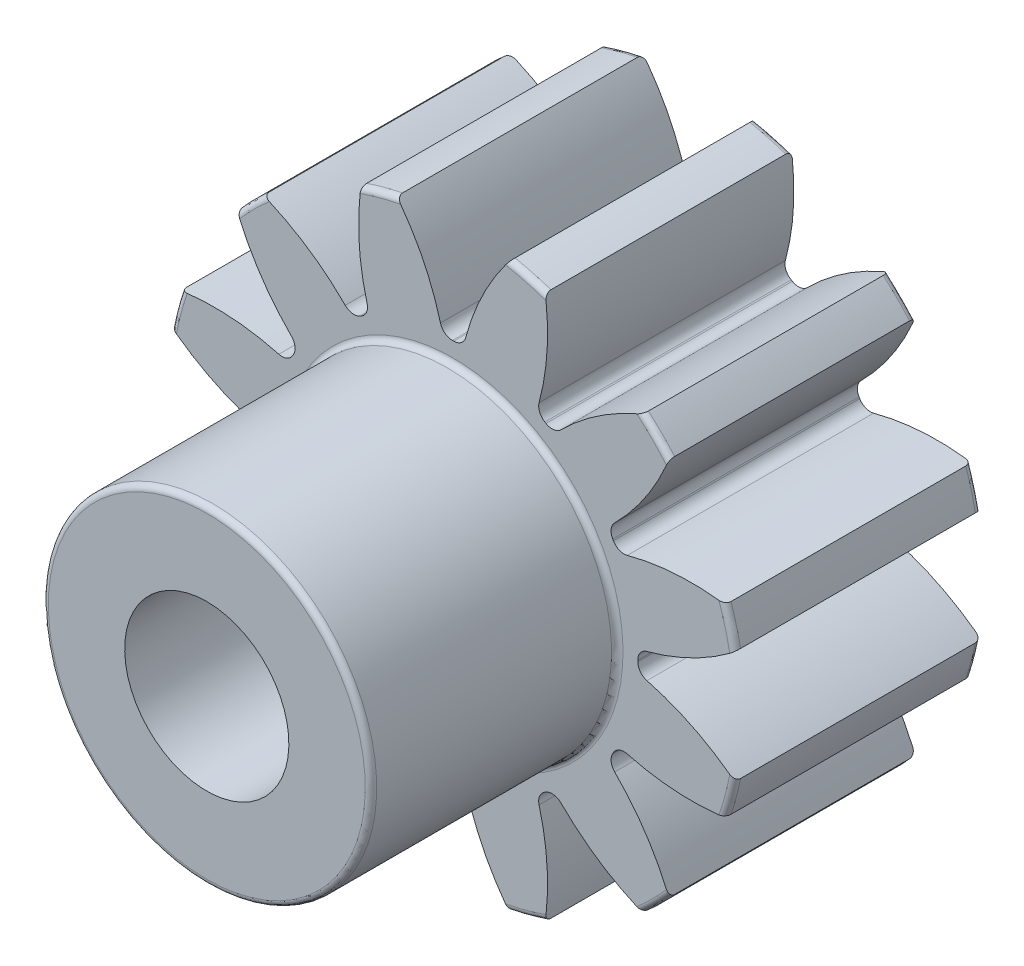
SolidWorks part; units mm, degrees
material "Delrin 2700 NC010, Low Viscosity Acetal Copolymer (SS)"
ref_plane "Front Plane" through (0, 0, 0) normal (0, 0, 1) x (1, 0, 0)
ref_plane "Top Plane" through (0, 0, 0) normal (0, 1, 0) x (1, 0, 0)
ref_plane "Right Plane" through (0, 0, 0) normal (1, 0, 0) x (0, 0, -1)
sketch "Sketch1" plane through (0, 0, 0) normal (0, 0, 1) x (1, 0, 0)
  line L0 (-152.4, 0) -> (152.4, 0) construction
  circle A0 centre (0, 0) radius 7 construction
  circle A1 centre (0, 0) radius 6 construction
  circle A2 centre (0, 0) radius 4.5 construction
  circle A3 centre (0, 0) radius 4 construction
  circle A4 centre (0, 0) radius 2 construction
  dimension "D2" = 1
  dimension "D3" = 2.5
  dimension "D1" = 2.5
sketch "Sketch2" plane through (0, 0, 0) normal (1, 0, 0) x (0, 0, -1)
  line L0 (0, 0) -> (-6, 0) construction
  line L1 (-6, 0) -> (-12, 0) construction
  dimension "Overall Width" = 12
  dimension "Face Width" = 6
sketch "Sketch4" plane through (0, 0, 0) normal (1, 0, 0) x (0, 0, -1)
  line L0 (-12, 2) -> (-12, 4)
  line L1 (-12, 4) -> (-6, 4)
  line L2 (-6, 4) -> (-6, 7)
  line L3 (-6, 7) -> (0, 7)
  line L4 (0, 7) -> (0, 2)
  line L5 (-6, 4) -> (-6, 0) construction
  line L6 (0, 7) -> (0, -7) construction
  line L7 (-6, 4) -> (0, 4) construction
  line L12 (-12, 2) -> (0, 2)
revolve "Revolve1" add sketch "Sketch4" angle 360 about L1
fillet "Fillet2" radius 0.14 4 edges at (0, 4, 12) (0, 4, 6) (0, 7, 6) (0, 7, 0)
sketch "Sketch7" plane through (0, 0, 6) normal (0, 0, 1) x (1, 0, 0)
  line L0 (0, 0) -> (0, 7) construction
  line L1 (0.7832, 5.9487) -> (1.27, 6.8838) construction
  line L3 (1.8117, 6.7615) -> (1.5529, 5.7956) construction
  line L4 (1.5529, 5.7956) -> (1.1647, 4.3467) construction
  line L5 (0, 0) -> (1.1647, 4.3467) construction
  line L6 (0.7832, 5.9487) -> (0, 0) construction
  line L7 (0.7832, 5.9487) -> (0.9137, 6.9401) construction
  line L8 (0.7832, 5.9487) -> (0, 0) construction
  circle A0 centre (0, 0) radius 7 construction
  arc A1 (-0.0164, 4.5) -> (0.0164, 4.5) centre (0, 0) cw
  circle A2 centre (0, 0) radius 4.5 construction
  arc A3 (-0.7832, 5.9487) -> (0.7832, 5.9487) centre (0, 0) cw construction
  circle A4 centre (0, 0) radius 6 construction
  arc A5 (2.2448, 6.6303) -> (1.3711, 6.8644) centre (0, 0) ccw construction
  arc A6 (0.7832, 5.9487) -> (2.2961, 5.5433) centre (0, 0) cw construction
  arc A7 (-1.3711, 6.8644) -> (1.3711, 6.8644) centre (0, 0) cw
  arc A8 (0.3074, 4.7228) -> (1.3711, 6.8644) centre (6.1052, 3.1782) cw
  arc A9 (-0.3074, 4.7228) -> (-1.3711, 6.8644) centre (-6.1052, 3.1782) ccw
  arc A10 (-0.0164, 4.5) -> (-0.3074, 4.7228) centre (-0.0175, 4.8) cw
  arc A11 (0.0164, 4.5) -> (0.3074, 4.7228) centre (0.0175, 4.8) ccw
  point P26 (-0.2511, 4.493)
  point P29 (0.2511, 4.493)
  dimension "D4" = 0.3
  dimension "D5" = 6
  dimension "D3" = 20
  dimension "D1" = 3.1416
  dimension "D2" = 1.5708
extrude "Cut-Extrude2" cut sketch "Sketch7" against normal through all
pattern_circular "CirPattern1" count 12 over 360 about axis through (0, 0, 12) along (0, 0, -1) of "Cut-Extrude2"
equation "\"D1@Sketch1\"=2.5*(\"Pitch Dia.@Sketch1\"/\"Number of Teeth@Sketch1\")"
equation "\"D1@CirPattern1\"=\"Number of Teeth@Sketch1\""
equation "\"D1@Fillet2\"=\"OD@Sketch1\"*.01"
equation "\"D1@Sketch7\"=3.14159*(\"Pitch Dia.@Sketch1\"/\"Number of Teeth@Sketch1\")"
equation "\"D2@Sketch7\"=\"D1@Sketch7\"/2"
equation "\"D4@Sketch7\"=\"D1@Sketch7\"*.0955"
equation "\"D5@Sketch7\"=\"Pitch Dia.@Sketch1\"/2"
